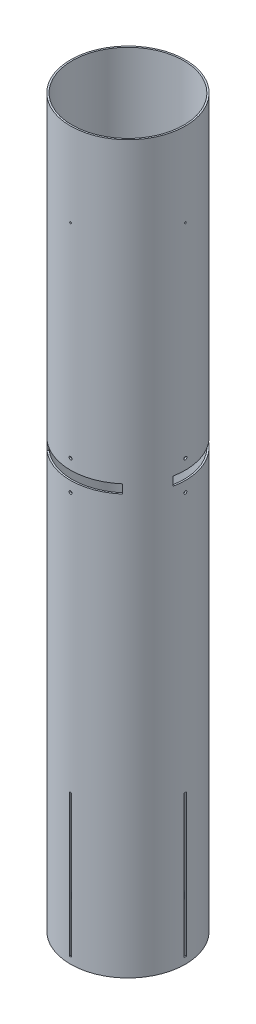
SolidWorks part; units mm, degrees
material "A-Glass Fiber"
ref_plane "Front Plane" through (0, 0, 0) normal (0, 0, 1) x (1, 0, 0)
ref_plane "Top Plane" through (0, 0, 0) normal (0, 1, 0) x (1, 0, 0)
ref_plane "Right Plane" through (0, 0, 0) normal (1, 0, 0) x (0, 0, -1)
sketch "Sketch1" plane through (0, 0, 0) normal (0, 1, 0) x (1, 0, 0)
  circle A0 centre (0, 0) radius 76.2
  circle A1 centre (0, 0) radius 78.359
  dimension "D1" = 152.4
  dimension "D2" = 156.718
extrude "Boss-Extrude1" add sketch "Sketch1" along normal blind 990.6
ref_plane "Plane1" through (0, 0, 0) normal (0.7071, 0, 0.7071) x (0.7071, 0, -0.7071)
ref_axis "Axis1" through (0, 990.6, 0) along (0, -1, 0)
sketch "Sketch2" plane through (0, 0, 0) normal (1, 0, 0) x (0, 0, -1)
  line L0 (0, 0) -> (0, 8.89)
  line L1 (1.5875, 8.89) -> (-1.5875, 8.89)
  line L2 (1.5875, 8.89) -> (1.5875, 203.2)
  line L3 (1.5875, 203.2) -> (-1.5875, 203.2)
  line L4 (-1.5875, 8.89) -> (-1.5875, 203.2)
  line L5 (1.5875, 8.89) -> (-1.5875, 203.2) construction
  line L6 (1.5875, 203.2) -> (-1.5875, 8.89) construction
  line L7 (78.359, 990.6) -> (-78.359, 990.6) construction
  line L8 (78.359, 990.6) -> (-78.359, 990.6)
  line L9 (0, 990.6) -> (0, 598.17)
  line L10 (-78.359, 0) -> (78.359, 0) construction
  circle A0 centre (0, 598.17) radius 2
  circle A1 centre (0, 876.3) radius 1.0922
  point P0 (0, 106.045)
  dimension "D4" = 4
  dimension "D6" = 2.1844
  dimension "D1" = 3.175
  dimension "D2" = 194.31
  dimension "D5" = 598.17
  dimension "D3" = 203.2
  dimension "D7" = 114.3
extrude "Fin Slots" cut sketch "Sketch2" against normal through all contours L4 L1 L2 L3 region at (0, 106.045, 0)
pattern_circular "CirPattern1" count 4 over 360 about axis through (0, 0, 0) along (0, 1, 0) of "Fin Slots" reverse direction yes
extrude "Cut-Extrude2" cut sketch "Sketch2<3>" against normal through all contours A0 region at (0, 599.5442, -1.3742)
sketch "Sketch2<3>" plane through (0, 0, 0) normal (1, 0, 0) x (0, 0, -1) same geometry as "Sketch2"
pattern_circular "CirPattern2" count 4 over 360 about axis through (0, 990.6, 0) along (0, -1, 0) of "Cut-Extrude2"
sketch "Sketch3" plane through (0, 0, 0) normal (0.7071, 0, 0.7071) x (0.7071, 0, -0.7071)
  line L0 (0, 0) -> (0, 127) construction
  circle A0 centre (0, 127) radius 3.175
  dimension "D1" = 6.35
  dimension "D2" = 127
extrude "Cut-Extrude3" cut sketch "Sketch3" against normal through all
ref_plane "Plane3" through (0, 583.8825, 0) normal (0, 1, 0) x (1, 0, 0)
sketch "Sketch7" plane through (0, 583.8825, 0) normal (0, 1, 0) x (1, 0, 0)
  line L0 (0, 0) -> (-76.8534, -15.2871)
  line L1 (0, 0) -> (0, 93.232) construction
  line L2 (0, 0) -> (-25.1877, 74.2005)
  line L3 (-78.359, 0) -> (0, 0) construction
  arc A0 (-78.3335, 2) -> (-78.3335, -2) centre (0, 0) ccw construction
  circle A1 centre (0, 0) radius 76.2 construction
  circle A2 centre (0, 0) radius 78.359
  circle A3 centre (0, 0) radius 78.359
  circle A4 centre (0, 0) radius 76.2
  circle A5 centre (0, 0) radius 78.359 construction
  arc A6 (2, 78.3335) -> (-2, 78.3335) centre (0, 0) ccw construction
  arc A7 (-78.3335, 2) -> (-78.3335, -2) centre (0, 0) ccw
  arc A8 (2, 78.3335) -> (-2, 78.3335) centre (0, 0) ccw
  dimension "D1" = 82.5
  dimension "D3" = 11.25
  dimension "D2" = 0
extrude "Cut-Extrude4" cut sketch "Sketch7" against normal blind 12.065 contours A4 A3 L0 region at (-75.9984, 583.8825, 14.0521)
pattern_circular "CirPattern3" count 3 over 360 about axis through (0, 990.6, 0) along (0, -1, 0) of "Cut-Extrude4"
extrude "Shear Screw Holes" cut sketch "Sketch2<4>" against normal through all contours L9 A1 | L9 A1 region at (0, 876.3, -0.4635) region at (0, 876.3, 0.4635)
sketch "Sketch2<4>" plane through (0, 0, 0) normal (1, 0, 0) x (0, 0, -1) same geometry as "Sketch2"
pattern_circular "Shear Screw Pattern" count 4 over 360 about axis through (0, 990.6, 0) along (0, -1, 0) of "Shear Screw Holes"
pattern_linear "LPattern1" count 2 spacing 40.574 along (0, -1, 0) of "Cut-Extrude2", "CirPattern2"
equation "\"D1@Boss-Extrude1\" = \"Aft_Section_Length\""
equation "\"AB_Coupler_OD_Length\"= 1in"
equation "\"AB_Coupling_Section_Length\"= 0.375in"
equation "\"AB_Coupler_Length\"= \"AB_Coupler_OD_Length\" + \"AB_Coupling_Section_Length\" * 2"
equation "\"AB_Coupler_Num_Screws\"= 4"
equation "\"AB_Coupling_Screw_Diameter\"= 0.15748in"
equation "\"Aft_Section_Length\"= 39in"
equation "\"D4@Sketch2\"=\"AB_Coupling_Screw_Diameter\""
equation "\"D1@CirPattern2\"=\"AB_Coupler_Num_Screws\""
equation "\"Rail_Nut_From_Bottom\"= 5in"
equation "\"Rail_Nut_Diam\"= 0.25in"
equation "\"D1@Sketch3\"=\"Rail_Nut_Diam\""
equation "\"D2@Sketch3\"=\"Rail_Nut_From_Bottom\""
equation "\"AB_BKHD_Thickness\"= 0.375in"
equation "\"AB_Mount_From_Bottom\"= 23.175in"
equation "\"Cutout_Angle\"= 80"
equation "\"Shear_Screw_Diameter\"= 0.086in"
equation "\"D6@Sketch2\"=\"Shear_Screw_Diameter\""
equation "\"Shear_Screw_Coupler_Location\"= 4.5in"
equation "\"D7@Sketch2\"=\"Shear_Screw_Coupler_Location\""
equation "\"Bodytube_OD\"= 6.17in"
equation "\"Bodytube_ID\"= 5.998in"
equation "\"Motor_OD\"= 4in"
equation "\"Fwd_Tube_Length\"= 40in"
equation "\"Mid_Tube_Length\"= 1in"
equation "\"Mid_Coupler_Length\"= 13in"
equation "\"AB_Paddle_Height\"= 0.375in"
equation "\"Num_Cutouts\"= 3"
equation "\"AB_Coupler_OD\"= 6.17in"
equation "\"AB_Coupler_ID\"= 5.75in"
equation "\"AB_Coupler_Surface_Diameter\"= 5.998in"
equation "\"AB_Central_Bushing_Length\"= .4724in"
equation "\"Lead_Screw_Dist\"= 3.4in"
equation "\"Lead_Screw_Diam\"= 0.386in"
equation "\"Lead_Screw_Length\"= (\"Mid_Coupler_Length\" + 2*0.375in + 2*0.5in)"
equation "\"Paddle_Pin_Offset\"= .25in"
equation "\"Paddle_Pin_Radius\"= 2.25in"
equation "\"SS_Paddle_Pin_Radius\"= 2.25*0.66in"
equation "\"Paddle_Gear_OD\"= 3.2in"
equation "\"Drive_Gear_OD\"= 1.7in"
equation "\"Fwd_BKHD_From_Top\"= 18in"
equation "\"Fin_Thickness\"= .118in"
equation "\"Guiderail_Cutout_Diameter\"= 1.5in"
equation "\"DB9_Hole_Dist\"= 25mm"
equation "\"DB9_Relief_Width\"= 0.47in"
equation "\"DB9_Relief_Hole_Offset\"= 0.09in"
equation "\"Airbrakes_Wire_Hole_Dia\"= .25in"
equation "\"Airbrakes_Wire_Hole_Dist\"= 1.1in"
equation "\"Servo_Gear_Offset\"= 0.5in"
equation "\"D3@LPattern1\"=\"AB_Central_Bushing_Length\"+\"AB_Coupling_Section_Length\"+0.75"
